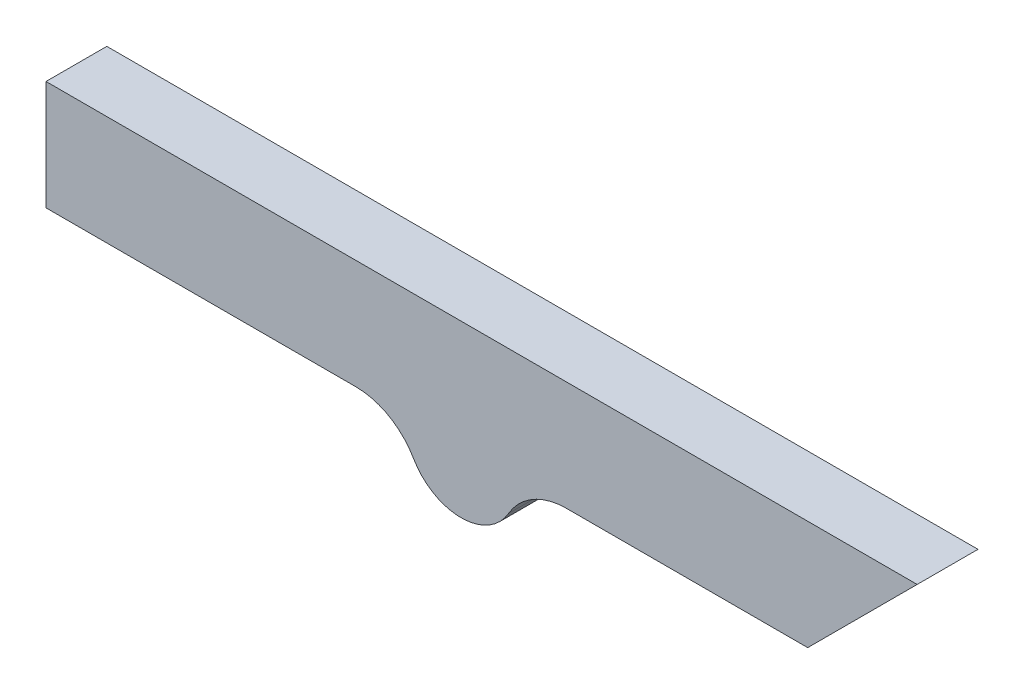
SolidWorks part; units mm, degrees
ref_plane "Front Plane" through (0, 0, 0) normal (0, 0, 1) x (1, 0, 0)
ref_plane "Top Plane" through (0, 0, 0) normal (0, 1, 0) x (1, 0, 0)
ref_plane "Right Plane" through (0, 0, 0) normal (1, 0, 0) x (0, 0, -1)
sketch "Sketch1" plane through (0, 0, 0) normal (0, 0, 1) x (1, 0, 0)
  line L0 (22.9331, 13.175) -> (11.75, 13.175)
  line L1 (11.75, 13.175) -> (11.75, 11.375)
  line L2 (11.75, 11.375) -> (13.8429, 11.375)
  line L3 (17.3071, 11.375) -> (21.1331, 11.375)
  line L4 (21.1331, 11.375) -> (22.9331, 13.175)
  line L5 (21.1745, 11.275) -> (23.1745, 13.275)
  line L6 (23.1745, 13.275) -> (11.65, 13.275)
  line L7 (11.65, 13.275) -> (11.65, 11.275)
  line L8 (11.65, 11.275) -> (13.8429, 11.275)
  line L9 (17.3071, 11.275) -> (21.1745, 11.275)
  line L10 (21.1745, 11.275) -> (23.1745, 13.275)
  line L11 (23.1745, 13.275) -> (11.65, 13.275)
  line L12 (11.65, 13.275) -> (11.65, 11.275)
  line L13 (11.65, 11.275) -> (13.8429, 11.275)
  line L14 (17.3071, 11.275) -> (21.1745, 11.275)
  line L15 (22.9331, 13.175) -> (23.0745, 13.175)
  line L16 (11.75, 13.175) -> (8.75, 13.175)
  line L17 (11.75, 13.175) -> (11.75, 11.375)
  line L18 (11.75, 11.375) -> (8.75, 11.375)
  line L19 (21.1331, 11.375) -> (21.2745, 11.375)
  line L29 (8.75, 13.175) -> (8.75, 11.375)
  arc A0 (14.7956, 10.825) -> (13.8429, 11.375) centre (13.8429, 10.275) ccw
  arc A1 (14.7956, 10.825) -> (16.3544, 10.825) centre (15.575, 11.275) ccw
  arc A2 (17.3071, 11.375) -> (16.3544, 10.825) centre (17.3071, 10.275) ccw
  arc A7 (14.709, 10.775) -> (13.8429, 11.275) centre (13.8429, 10.275) ccw
  arc A8 (14.709, 10.775) -> (16.441, 10.775) centre (15.575, 11.275) ccw
  arc A9 (17.3071, 11.275) -> (16.441, 10.775) centre (17.3071, 10.275) ccw
  arc A10 (14.709, 10.775) -> (13.8429, 11.275) centre (13.8429, 10.275) ccw
  arc A11 (14.709, 10.775) -> (16.441, 10.775) centre (15.575, 11.275) ccw
  arc A12 (17.3071, 11.275) -> (16.441, 10.775) centre (17.3071, 10.275) ccw
  dimension "D3" = 3
  dimension "D1" = 0
  dimension "D2" = 0.1
extrude "Shape" add sketch "Sketch1" along normal blind 1 contours A2 L3 L4 L0 L1 L2 A0 A1 | L4 L19 L10 L15 | L18 L1 L16 L12 | L16 L29 L18 L12 region at (16.7953, 12.1929, 0) region at (22.1038, 12.275, 0) region at (11.7, 12.275, 0) region at (10.2, 12.275, 0)
